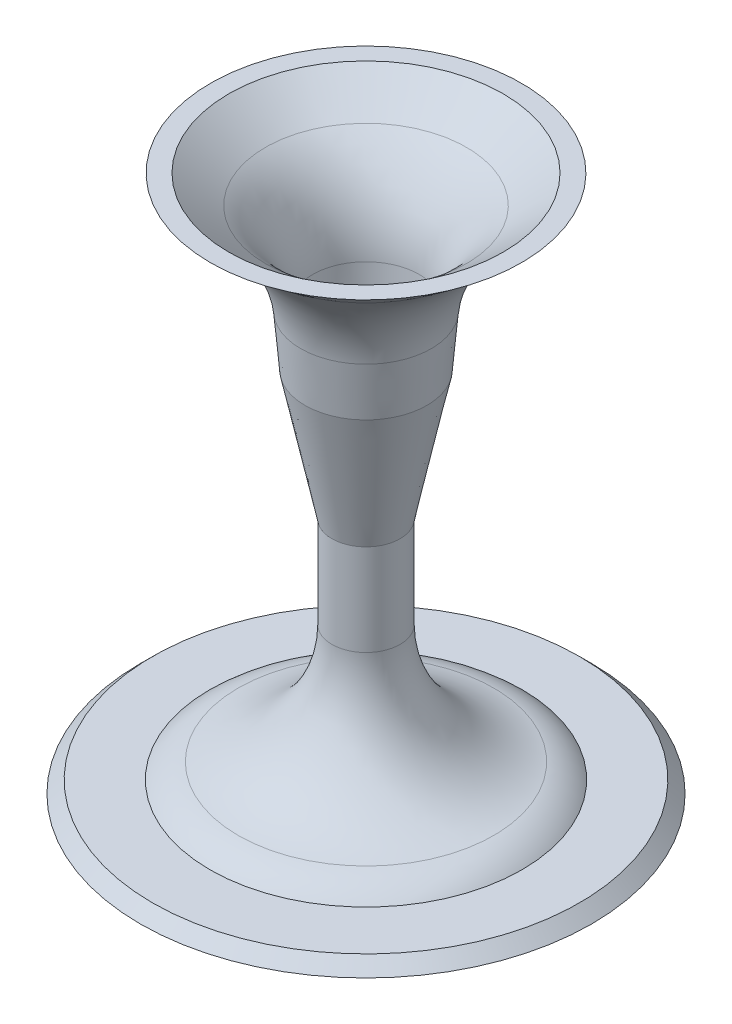
SolidWorks part; units mm, degrees
ref_plane "Front Plane" through (0, 0, 0) normal (0, 0, 1) x (1, 0, 0)
ref_plane "Top Plane" through (0, 0, 0) normal (0, 1, 0) x (1, 0, 0)
ref_plane "Right Plane" through (0, 0, 0) normal (1, 0, 0) x (0, 0, -1)
sketch "Sketch1" plane through (0, 0, 0) normal (0, 0, 1) x (1, 0, 0)
  line L0 (0, 74.3905) -> (0, -74.3905) construction
  line L2 (-3.59, -36.15) -> (-3.59, -21.15)
  line L3 (-3.59, -21.15) -> (-8, 0)
  line L4 (-8, 0) -> (-8.7663, 9.1953)
  line L5 (-8, 0) -> (0, 0) construction
  line L6 (-9.5, 18) -> (0, 18) construction
  line L7 (-16.503, 23.3869) -> (-22.5, 28)
  line L8 (-22.5, 28) -> (0, 28) construction
  line L10 (-5.59, -36.15) -> (-5.59, -21.15)
  line L11 (-5.59, -21.15) -> (-10.0038, 0)
  line L12 (-10.0038, 0) -> (-10.7159, 8.415)
  line L13 (-18.4556, 22.5849) -> (-25.5, 28)
  line L15 (-25.5, 28) -> (-22.5, 28)
  line L17 (-25.59, -56.15) -> (-25.59, -58.15)
  line L19 (-16.4248, -56.15) -> (-16.4248, -58.15)
  line L20 (-25.59, -58.15) -> (-35, -58.15)
  line L23 (-37, -60.15) -> (0, -60.15)
  line L24 (0, -60.15) -> (0, -58.15)
  line L25 (-2.0265, -58.15) -> (-16.4248, -58.15)
  line L26 (-35, -58.15) -> (-37, -60.15)
  line L27 (-3.59, -36.15) -> (0, -58.15)
  line L29 (-2.0265, -58.15) -> (-4.5614, -42.6153)
  arc A0 (-10.7159, 8.415) -> (-18.4556, 22.5849) centre (-30.6447, 6.7284) ccw
  arc A1 (-8.7663, 9.1953) -> (-16.503, 23.3869) centre (-28.6972, 7.5344) ccw
  arc A2 (-25.59, -56.15) -> (-5.59, -36.15) centre (-25.59, -36.15) ccw
  arc A3 (-4.5614, -42.6153) -> (-16.4248, -56.15) centre (-25.59, -36.15) cw
  point P4 (0, 0)
  point P20 (-37, -58.15)
  point P34 (0, -54.3988)
  dimension "D2" = 2
  dimension "D10" = 20
  dimension "D12" = 20
  dimension "D9" = 2
  dimension "D13" = 2
  dimension "D14" = 15
  dimension "D23" = 2
  dimension "D3" = 21.15
  dimension "D4" = 16
  dimension "D5" = 19
  dimension "D6" = 18
  dimension "D7" = 45
  dimension "D8" = 10
  dimension "D11" = 7.18
  dimension "D15" = 2.0038
  dimension "D16" = 3
  dimension "D17" = 2.1
  dimension "D18" = 18.4556
  dimension "D19" = 2
  dimension "D20" = 45
  dimension "D21" = 2
  dimension "D22" = 37
  dimension "D24" = 2
revolve "Revolve2" add sketch "Sketch1" angle 360 about L0
fillet "Fillet1" radius 10 1 edges at (0, -56.15, 25.59)
sketch "Sketch3" plane through (0, 0, 0) normal (0, 1, 0) x (1, 0, 0)
  line L0 (0, -64.9001) -> (0, 56.1755) construction
ref_plane "Plane1" through (0, 0, 0) normal (0.2079, 0.9781, 0) x (0, 0, -1)
